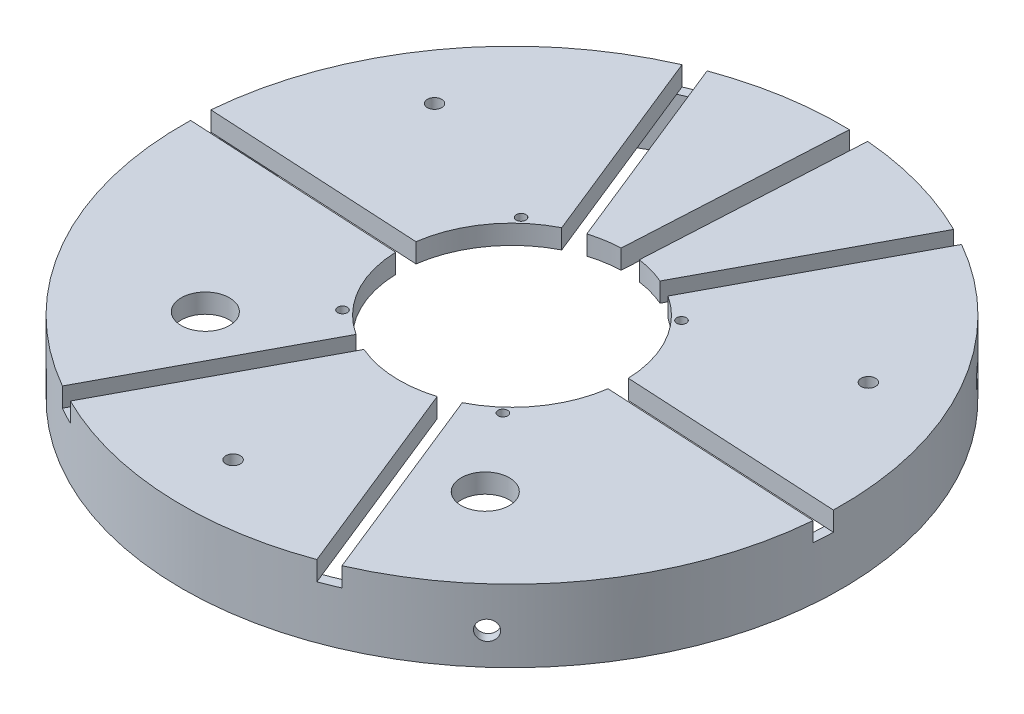
SolidWorks part; units mm, degrees
material "6061 Alloy"
ref_plane "Front Plane" through (0, 0, 0) normal (0, 0, 1) x (1, 0, 0)
ref_plane "Top Plane" through (0, 0, 0) normal (0, 1, 0) x (1, 0, 0)
ref_plane "Right Plane" through (0, 0, 0) normal (1, 0, 0) x (0, 0, -1)
sketch "Sketch1" plane through (0, 0, 0) normal (0, 1, 0) x (-0.9986, 0, -0.0535)
  line L0 (55.4987, 41.0091) -> (55.4987, 34.0091) construction
  line L2 (55.4987, -32.3449) -> (55.4987, -2.3278) construction
  circle A1 centre (55.4987, -32.3449) radius 68.37
  circle A3 centre (55.4987, -32.3449) radius 23.401
extrude "Boss-Extrude1" add sketch "Sketch1" along normal blind 2
sketch "Sketch3" plane through (0, 2, 0) normal (0, 1, 0) x (1, 0, 0)
  circle A0 centre (-53.6871, 35.2703) radius 68.37
  circle A1 centre (-53.6871, 35.2703) radius 66.37
extrude "Boss-Extrude2" add sketch "Sketch3" against normal blind 13
sketch "Sketch24" [suppressed] plane through (0, 4.3, 0) normal (0, 1, 0) x (1, 0, 0)
  line L0 (-34.4111, 2.0274) -> (-34.9466, -7.9582) construction
  line L1 (25.902, -11.2211) -> (26.4375, -1.2355) construction
  point P0 (-34.6788, -2.9654)
  point P1 (26.1698, -6.2283)
sketch "Sketch25" [suppressed] plane through (0, 0, 0) normal (0, -1, 0) x (1, 0, 0)
  point P0 (-34.6788, 2.9654)
  point P1 (26.1698, 6.2283)
ref_plane "Plane1" [suppressed] through (-0.258, 0, 4.8112) normal (0.0535, 0, -0.9986) x (-0.9986, 0, -0.0535)
sketch "Sketch29" [suppressed] plane through (0, 4.3, 0) normal (0, 1, 0) x (1, 0, 0)
  arc A0 (18.841, -0.8281) -> (-26.8146, 1.6201) centre (-4.2545, -4.5968) ccw construction
  arc A1 (-27.3501, -8.3656) -> (18.3055, -10.8138) centre (-4.2545, -4.5968) ccw construction
  point P0 (-3.0015, 18.7706)
  point P1 (-5.5076, -27.9643)
sketch "Sketch30" [suppressed] plane through (0, 0, 0) normal (0, -1, 0) x (1, 0, 0)
  point P0 (-5.5076, 27.9643)
  point P1 (-3.0015, -18.7706)
ref_plane "Plane2" [suppressed] through (-3.9965, 0, -0.2143) normal (-0.9986, 0, -0.0535) x (-0.0535, 0, 0.9986)
sketch "Sketch35" [suppressed] plane through (0, 0, 0) normal (0, 1, 0) x (1, 0, 0)
  line L0 (-3.8699, 2.5759) -> (-4.1232, -2.1473) construction
  line L1 (2.1036, -4.9378) -> (-2.6196, -4.6845) construction
  line L2 (20.5267, 17.662) -> (-4.2545, -4.5968) construction
  line L3 (-4.2545, -4.5968) -> (-31.1135, -28.7219) construction
  arc A1 (-27.3501, -8.3656) -> (18.3055, -10.8138) centre (-4.2545, -4.5968) ccw construction
  point P0 (-4.2545, -4.5968)
  point P8 (20.5267, 17.662)
  point P10 (-21.6638, -20.2341)
sketch "Sketch36" [suppressed] plane through (0, 4.3, 0) normal (0, 1, 0) x (1, 0, 0)
  point P0 (20.5267, 17.662)
ref_plane "Plane3" [suppressed] through (0.3855, 0, 0.4291) normal (0.6682, 0, 0.744) x (0.744, 0, -0.6682)
sketch "Sketch37" [suppressed] plane through (0, 4.3, 0) normal (0, 1, 0) x (1, 0, 0)
  line L1 (-26.6296, 20.3138) -> (-4.2545, -4.5968) construction
  line L2 (-4.2545, -4.5968) -> (20.7564, -32.4421) construction
  point P0 (-4.2545, -4.5968)
  point P7 (-26.6296, 20.3138)
sketch "Sketch39" [suppressed] plane through (0, 0, 0) normal (0, -1, 0) x (1, 0, 0)
  point P0 (-26.6296, -20.3138)
ref_plane "Plane4" [suppressed] through (-4.64, 0, 4.1677) normal (-0.744, 0, 0.6682) x (0.6682, 0, 0.744)
sketch "Sketch40" [suppressed] plane through (0.3855, 0, 0.4291) normal (0.6682, 0, 0.744) x (0.744, 0, -0.6682)
  circle A0 centre (-6.2369, -3.85) radius 2
extrude "Cut-Extrude27" [suppressed] cut sketch "Sketch40" against normal through all
pattern_circular "CirPattern2" [suppressed] count 4 over 360 reverse direction yes of bodies 107
sketch "Sketch58" plane through (0, 2, 0) normal (0, 1, 0) x (1, 0, 0)
  line L2 (-12.7238, 29.0656) -> (-12.2954, 37.0565)
  line L3 (-12.2954, 37.0565) -> (-7.3025, 36.7887)
  line L4 (-7.3025, 36.7887) -> (-7.731, 28.7979)
  line L5 (-7.731, 28.7979) -> (-12.7238, 29.0656)
sketch "Sketch60" plane through (0, 2, 0) normal (0, 1, 0) x (1, 0, 0)
  line L0 (-52.2437, 62.1872) -> (-55.1305, 8.3534) construction
  line L1 (-84.1539, 36.904) -> (-23.2203, 33.6365) construction
  line L4 (-73.7408, 17.2578) -> (-104.5394, -10.4059) construction
  line L5 (-53.6871, 35.2703) -> (-73.7408, 17.2578) construction
  line L6 (-71.6996, 55.324) -> (-99.3633, 86.1226) construction
  line L7 (-53.6871, 35.2703) -> (-71.6996, 55.324) construction
  line L8 (-33.6334, 53.2828) -> (-2.8348, 80.9464) construction
  line L9 (-53.6871, 35.2703) -> (-33.6334, 53.2828) construction
  line L10 (-35.6746, 15.2165) -> (-8.0109, -15.5821) construction
  line L11 (-53.6871, 35.2703) -> (-35.6746, 15.2165) construction
  line L12 (-73.7408, 17.2578) -> (-104.5394, -10.4059) construction
  line L13 (-53.6871, 35.2703) -> (-73.7408, 17.2578) construction
  arc A1 (-55.1305, 8.3534) -> (-80.604, 36.7136) centre (-53.6871, 35.2703) cw
  dimension "D1" = 4
sketch "Sketch62" plane through (0, 0, 0) normal (0, -1, 0) x (1, 0, 0)
  line L0 (-8.0109, 15.5821) -> (-99.3633, -86.1226) construction
  line L1 (-104.5394, 10.4059) -> (-2.8348, -80.9464) construction
  point P9 (-53.6871, -35.2703)
ref_plane "Plane5" through (-41.5069, 0, -46.2106) normal (0.6682, 0, 0.744) x (0.744, 0, -0.6682)
ref_plane "Plane6" through (-12.1802, 0, 10.9404) normal (0.744, 0, -0.6682) x (-0.6682, 0, -0.744)
sketch "Sketch63" plane through (-41.5069, 0, -46.2106) normal (0.6682, 0, 0.744) x (0.744, 0, -0.6682)
  line L0 (-84.7262, 0) -> (51.9818, 0) construction
  line L3 (-16.3722, 0) -> (-16.3722, -8.7) construction
  circle A0 centre (-16.3722, -4.35) radius 2
extrude "Cut-Extrude40" cut sketch "Sketch63" against normal through all and the other way through all
sketch "Sketch64" plane through (-12.1802, 0, 10.9404) normal (0.744, 0, -0.6682) x (-0.6682, 0, -0.744)
  line L0 (-6.2392, 0) -> (130.4688, 0) construction
  line L3 (62.1148, 0) -> (62.1148, -8.7) construction
  circle A0 centre (62.1148, -4.35) radius 2
extrude "Cut-Extrude41" cut sketch "Sketch64" against normal through all and the other way through all
sketch "Sketch65" plane through (0, 2, 0) normal (0, -1, 0) x (1, 0, 0)
  line L2 (1.1947, -31.5296) -> (-6.7555, -31.9265)
  line L3 (0.4048, -1118.9656) -> (-50.8954, -91.2006) construction
  line L4 (1.2944, -33.5271) -> (-6.7555, -33.9289)
  line L5 (-108.5689, -39.0109) -> (-100.6187, -38.6141)
  line L6 (-108.6686, -37.0134) -> (-100.6187, -36.6116)
  line L7 (-49.9465, -90.152) -> (-50.3433, -82.2019)
  line L8 (-51.944, -90.2517) -> (-52.3458, -82.2019)
  line L16 (-57.4277, 19.6115) -> (-57.0309, 11.6614) [skipped]
  line L17 (-55.4302, 19.7112) -> (-55.0284, 11.6614) [skipped]
  arc A2 (1.2944, -33.5271) -> (1.1947, -31.5296) centre (1.2445, -32.5284) ccw
  arc A3 (-6.7555, -33.9289) -> (-6.7555, -31.9265) centre (-6.8055, -32.9277) cw
  arc A4 (-51.944, -90.2517) -> (-49.9465, -90.152) centre (-50.9452, -90.2019) ccw
  arc A5 (-52.3458, -82.2019) -> (-50.3433, -82.2019) centre (-51.3445, -82.1519) cw
  arc A6 (-108.6686, -37.0134) -> (-108.5689, -39.0109) centre (-108.6187, -38.0121) ccw
  arc A7 (-100.6187, -36.6116) -> (-100.6187, -38.6141) centre (-100.5687, -37.6128) cw
  arc A16 (-55.4302, 19.7112) -> (-57.4277, 19.6115) centre (-56.429, 19.6614) ccw [skipped]
  arc A17 (-55.0284, 11.6614) -> (-57.0309, 11.6614) centre (-56.0297, 11.6114) cw [skipped]
  dimension "D1" = 4
sketch "Sketch67" plane through (0, 2, 0) normal (0, 1, 0) x (1, 0, 0)
  line L0 (-99.6611, 37.7404) -> (-7.7126, 32.8099) construction
  line L1 (-51.2218, 81.2445) -> (-56.1524, -10.704) construction
  line L2 (-47.8311, 125.7094) -> (-49.8283, 125.8165)
  line L3 (-144.1262, 41.1262) -> (-144.2333, 39.1291)
  line L4 (-99.6075, 38.739) -> (-144.1262, 41.1262)
  line L5 (-99.7146, 36.7419) -> (-144.2333, 39.1291)
  line L6 (-50.2184, 81.1907) -> (-47.8311, 125.7094)
  line L7 (-52.2155, 81.2978) -> (-49.8283, 125.8165)
  line L8 (36.752, 29.4143) -> (36.8591, 31.4114)
  line L9 (-7.7667, 31.8015) -> (36.752, 29.4143)
  line L10 (-7.6596, 33.7987) -> (36.8591, 31.4114)
  line L49 (-59.5431, -55.1689) -> (-57.5459, -55.276) [skipped]
  line L50 (-57.1558, -10.6501) -> (-59.5431, -55.1689) [skipped]
  line L51 (-55.1587, -10.7572) -> (-57.5459, -55.276) [skipped]
  arc A1 (-99.6075, 38.739) -> (-99.7146, 36.7419) centre (-99.6611, 37.7404) cw
  arc A2 (-50.2184, 81.1907) -> (-52.2155, 81.2978) centre (-51.2169, 81.2442) cw
  arc A3 (-7.7667, 31.8015) -> (-7.6596, 33.7987) centre (-7.7132, 32.8001) cw
  arc A8 (-57.1558, -10.6501) -> (-55.1587, -10.7572) centre (-56.1573, -10.7037) cw [skipped]
  dimension "D1" = 4
extrude "Cut-Extrude45" cut sketch "Sketch67" against normal blind 2
sketch "Sketch70" plane through (0, 2, 0) normal (0, 1, 0) x (1, 0, 0)
  line L0 (-51.2169, 81.2442) -> (-53.6871, 35.2703) construction
  line L1 (-99.6611, 37.7404) -> (-7.7132, 32.8001) construction
  line L2 (-53.6871, 35.2703) -> (-56.5307, -17.6534) construction
  circle A0 centre (-99.7745, 65.2862) radius 1.5
  circle A1 centre (-56.638, -19.6505) radius 1.5
  circle A2 centre (-4.6489, 60.1751) radius 1.5
  dimension "D1" = 3
  dimension "D2" = 3
sketch "Sketch72" plane through (0, 2, 0) normal (0, 1, 0) x (1, 0, 0)
  line L0 (-51.2169, 81.2442) -> (-56.638, -19.6505) construction
  line L1 (-99.6611, 37.7404) -> (-7.7132, 32.8001) construction
sketch "Sketch73" plane through (0, 2, 0) normal (0, -1, 0) x (1, 0, 0)
  circle A0 centre (-72.2141, -18.6326) radius 1
  circle A1 centre (-37.0495, -16.7433) radius 1
  circle A2 centre (-35.1601, -51.9079) radius 1
  circle A3 centre (-70.3247, -53.7973) radius 1
extrude "Cut-Extrude47" cut sketch "Sketch73" along normal blind 10
extrude "Cut-Extrude48" cut sketch "Sketch70" against normal blind 10
extrude "Cut-Extrude49" cut sketch "Sketch74" against normal blind 10
sketch "Sketch74" plane through (19.5625, 3, -2.0536) normal (0, 1, 0) x (1, 0, 0)
  line L0 (-73.2496, 33.2167) -> (-76.2005, -21.7041) construction
  line L1 (-73.2496, 33.2167) -> (-44.3242, -1.2553) construction
  line L2 (-73.2496, 33.2167) -> (-105.7022, 2.0425) construction
  circle A0 centre (-105.7022, 2.0425) radius 5
  circle A1 centre (-44.3242, -1.2553) radius 5
sketch "Sketch75" plane through (0, 2, 0) normal (0, 1, 0) x (1, 0, 0)
  line L0 (-50.0757, 102.5274) -> (-51.2185, 81.2443) construction
  line L1 (-120.9442, 38.8817) -> (13.57, 31.6588) construction
  line L2 (-86.2666, -23.6885) -> (-88.9936, -28.8014)
  line L3 (-22.8723, 95.1703) -> (-32.9078, 76.3546)
  line L4 (-21.1076, 94.229) -> (-31.1431, 75.4134)
  line L5 (-88.9936, -28.8014) -> (-87.2289, -29.7426)
  line L6 (-53.5602, 37.6331) -> (-58.8341, -60.585) construction
  line L7 (-52.5853, 35.2111) -> (-52.8048, 34.7997)
  line L8 (-84.5019, -24.6297) -> (-87.2289, -29.7426)
  line L9 (-79.7658, 97.3787) -> (-83.5737, 106.8386)
  line L10 (-53.5602, 37.6331) -> (-54.5694, 35.7409)
  line L11 (-77.9105, 98.1256) -> (-82.0529, 108.4166)
  line L12 (-79.7658, 97.3787) -> (-71.8029, 77.5967)
  line L13 (-22.8723, 95.1703) -> (-17.9091, 104.4757)
  line L14 (-77.9105, 98.1256) -> (-69.9475, 78.3435)
  line L15 (-27.6084, -26.8382) -> (-35.5714, -7.0562)
  line L16 (-21.1076, 94.229) -> (-18.0109, 100.0352)
  line L17 (-29.4638, -27.5851) -> (-37.4267, -7.803)
  line L18 (-29.4638, -27.5851) -> (-27.0828, -33.5)
  line L19 (-84.5019, -24.6297) -> (-74.4664, -5.8141)
  line L20 (-86.2666, -23.6885) -> (-76.2311, -4.8729)
  line L21 (-27.6084, -26.8382) -> (-25.2275, -32.7531)
  line L22 (-25.2275, -32.7531) -> (-27.0828, -33.5)
  line L23 (-83.5737, 106.8386) -> (-82.0529, 108.4166)
  line L24 (-17.9091, 104.4757) -> (-18.0109, 100.0352)
  arc A3 (-32.9078, 76.3546) -> (-31.1431, 75.4134) centre (-32.0254, 75.884) ccw
  arc A4 (-69.9475, 78.3435) -> (-71.8029, 77.5967) centre (-70.8752, 77.9701) cw
  arc A5 (-37.4267, -7.803) -> (-35.5714, -7.0562) centre (-36.499, -7.4296) cw
  arc A6 (-74.4664, -5.8141) -> (-76.2311, -4.8729) centre (-75.3488, -5.3435) ccw
extrude "Cut-Extrude51" cut sketch "Sketch75" against normal blind 2 contours A4 L14 L12 | L3 A3 L4 | L19 A6 L20 | A5 L17 L15 region at (-81.5448, 2, 16.9605) region at (-25.1869, 2, -88.7515) region at (-76.6935, 2, -92.4365) region at (-31.4741, 2, 19.913)
sketch "Sketch80" plane through (0, 2, 0) normal (0, 1, 0) x (1, 0, 0)
  line L0 (-121.8978, 39.9343) -> (-99.6075, 38.739)
  line L1 (-122.0051, 37.9371) -> (-99.7146, 36.7419)
  line L2 (-78.2871, 99.0613) -> (-69.9475, 78.3435)
  line L3 (-80.1424, 98.3145) -> (-71.8029, 77.5967)
  line L4 (-51.0202, 103.5882) -> (-52.2155, 81.2978)
  line L5 (-49.0231, 103.481) -> (-50.2184, 81.1907)
  line L6 (-22.3976, 96.0603) -> (-32.9078, 76.3546)
  line L7 (-20.6329, 95.119) -> (-31.1431, 75.4134)
  line L8 (-20.6329, 95.119) -> (-31.1431, 75.4134) construction
  line L9 (14.6309, 32.6034) -> (-7.6596, 33.7987)
  line L10 (-7.7667, 31.8015) -> (14.5236, 30.6063)
  line L11 (-86.7413, -24.5785) -> (-76.2311, -4.8729)
  line L12 (-74.4664, -5.8141) -> (-84.9766, -25.5197)
  line L13 (-37.4267, -7.803) -> (-29.0871, -28.5208)
  line L14 (-35.5714, -7.0562) -> (-27.2318, -27.7739)
  arc A0 (-80.1424, 98.3145) -> (-121.8978, 39.9343) centre (-53.6871, 35.2703) ccw
  circle A1 centre (-99.7745, 65.2862) radius 1.5
  circle A2 centre (-4.6489, 60.1751) radius 1.5
  circle A3 centre (-24.7617, 0.7983) radius 5
  circle A4 centre (-86.1397, 4.0961) radius 5
  circle A5 centre (-72.2141, 18.6326) radius 1
  circle A6 centre (-53.6871, 35.2703) radius 23.401
  circle A7 centre (-37.0495, 16.7433) radius 1
  circle A8 centre (-35.1601, 51.9079) radius 1
  circle A9 centre (-70.3247, 53.7973) radius 1
  arc A10 (-32.9078, 76.3546) -> (-31.1431, 75.4134) centre (-32.0254, 75.884) ccw construction
  circle A11 centre (-56.638, -19.6505) radius 1.5
  arc A12 (-7.7667, 31.8015) -> (-7.6596, 33.7987) centre (-7.7132, 32.8001) cw
  arc A13 (-32.9078, 76.3546) -> (-31.1431, 75.4134) centre (-32.0254, 75.884) ccw
  arc A14 (-52.2155, 81.2978) -> (-50.2184, 81.1907) centre (-51.2169, 81.2442) ccw
  arc A15 (-69.9475, 78.3435) -> (-71.8029, 77.5967) centre (-70.8752, 77.9701) cw
  arc A16 (-99.6075, 38.739) -> (-99.7146, 36.7419) centre (-99.6611, 37.7404) cw
  arc A17 (-74.4664, -5.8141) -> (-76.2311, -4.8729) centre (-75.3488, -5.3435) ccw
  arc A18 (-51.0202, 103.5882) -> (-78.2871, 99.0613) centre (-53.6871, 35.2703) ccw
  arc A19 (-76.2311, -4.8729) -> (-74.4664, -5.8141) centre (-75.3488, -5.3435) cw
  arc A20 (-35.5714, -7.0562) -> (-37.4267, -7.803) centre (-36.499, -7.4296) ccw
  arc A21 (-22.3976, 96.0603) -> (-49.0231, 103.481) centre (-53.6871, 35.2703) ccw
  arc A22 (14.6309, 32.6034) -> (-20.6329, 95.119) centre (-53.6871, 35.2703) ccw
  arc A23 (-27.2318, -27.7739) -> (14.5236, 30.6063) centre (-53.6871, 35.2703) ccw
  arc A24 (-84.9766, -25.5197) -> (-29.0871, -28.5208) centre (-53.6871, 35.2703) ccw
  arc A25 (-122.0051, 37.9371) -> (-86.7413, -24.5785) centre (-53.6871, 35.2703) ccw
  circle M1 centre (-24.7617, 0.7983) radius 5
  circle M2 centre (-86.1397, 4.0961) radius 5
  circle M3 centre (-4.6489, 60.1751) radius 1.5
  circle M4 centre (-99.7745, 65.2862) radius 1.5
  circle M5 centre (-56.638, -19.6505) radius 1.5
  circle M6 centre (-35.1601, 51.9079) radius 1
  circle M7 centre (-72.2141, 18.6326) radius 1
  circle M8 centre (-53.6871, 35.2703) radius 23.401
  circle M9 centre (-37.0495, 16.7433) radius 1
  circle M10 centre (-70.3247, 53.7973) radius 1
  arc M11 (-37.4267, -7.803) -> (-35.5714, -7.0562) centre (-36.499, -7.4296) cw
  line M12 (-35.5714, -7.0562) -> (-27.2318, -27.7739)
  arc M13 (-27.2318, -27.7739) -> (14.5236, 30.6063) centre (-53.6871, 35.2703) ccw
  line M14 (14.5236, 30.6063) -> (-7.7667, 31.8015)
  arc M15 (-7.7667, 31.8015) -> (-7.6596, 33.7987) centre (-7.7132, 32.8001) cw
  line M16 (-7.6596, 33.7987) -> (14.6309, 32.6034)
  arc M17 (14.6309, 32.6034) -> (-20.6329, 95.119) centre (-53.6871, 35.2703) ccw
  line M18 (-20.6329, 95.119) -> (-31.1431, 75.4134)
  arc M19 (-31.1431, 75.4134) -> (-32.9078, 76.3546) centre (-32.0254, 75.884) cw
  line M20 (-32.9078, 76.3546) -> (-22.3976, 96.0603)
  arc M21 (-22.3976, 96.0603) -> (-49.0231, 103.481) centre (-53.6871, 35.2703) ccw
  line M22 (-49.0231, 103.481) -> (-50.2184, 81.1907)
  arc M23 (-50.2184, 81.1907) -> (-52.2155, 81.2978) centre (-51.2169, 81.2442) cw
  line M24 (-52.2155, 81.2978) -> (-51.0202, 103.5882)
  arc M25 (-51.0202, 103.5882) -> (-78.2871, 99.0613) centre (-53.6871, 35.2703) ccw
  line M26 (-78.2871, 99.0613) -> (-69.9475, 78.3435)
  arc M27 (-69.9475, 78.3435) -> (-71.8029, 77.5967) centre (-70.8752, 77.9701) cw
  line M28 (-71.8029, 77.5967) -> (-80.1424, 98.3145)
  arc M29 (-80.1424, 98.3145) -> (-121.8978, 39.9343) centre (-53.6871, 35.2703) ccw
  line M30 (-121.8978, 39.9343) -> (-99.6075, 38.739)
  arc M31 (-99.6075, 38.739) -> (-99.7146, 36.7419) centre (-99.6611, 37.7404) cw
  line M32 (-99.7146, 36.7419) -> (-122.0051, 37.9371)
  arc M33 (-122.0051, 37.9371) -> (-86.7413, -24.5785) centre (-53.6871, 35.2703) ccw
  line M34 (-86.7413, -24.5785) -> (-76.2311, -4.8729)
  arc M35 (-76.2311, -4.8729) -> (-74.4664, -5.8141) centre (-75.3488, -5.3435) cw
  line M36 (-74.4664, -5.8141) -> (-84.9766, -25.5197)
  arc M37 (-84.9766, -25.5197) -> (-29.0871, -28.5208) centre (-53.6871, 35.2703) ccw
  line M38 (-29.0871, -28.5208) -> (-37.4267, -7.803)
extrude "Boss-Extrude4" add sketch "Sketch80" along normal blind 2 contours M38 M11 M12 M13 M14 M15 M16 M17 M18 M19 M20 M21 M22 M23 M24 M25 M26 M27 M28 M29 M30 M31 M32 M33 M34 M35 M36 M37 M2 M4 M6 M8 M10 M9 M7 M5 M3 M1 region at (-107.7243, 2, -73.9194)
sketch "Sketch81" plane through (0, 4, 0) normal (0, 1, 0) x (1, 0, 0)
  line L0 (-79.2175, 98.6947) -> (-28.1567, -28.1541) construction
  line L1 (-85.8624, -25.0556) -> (-21.5118, 95.5961) construction
  line L2 (14.5845, 31.6044) -> (-121.9588, 38.9361) construction
  line L3 (-50.0213, 103.5419) -> (-52.8071, 51.6586) construction
  line L4 (-79.2175, 98.6947) -> (-81.2506, 103.7454) construction
  line L5 (-50.0213, 103.5419) -> (-49.6564, 110.3364) construction
  line L6 (-21.5118, 95.5961) -> (-17.4008, 103.3039) construction
  line L7 (14.5845, 31.6044) -> (23.3386, 31.1344) construction
  line L8 (-28.1567, -28.1541) -> (-24.5898, -37.0153) construction
  line L9 (-85.8624, -25.0556) -> (-88.7119, -30.3981) construction
  line L10 (-121.9588, 38.9361) -> (-129.9907, 39.3674) construction
  line L11 (-81.0728, 97.9478) -> (-83.1059, 102.9986)
  line L12 (-81.0728, 97.9478) -> (-30.012, -28.901)
  line L13 (-30.012, -28.901) -> (-26.4451, -37.7621)
  line L14 (-52.0184, 103.6491) -> (-51.6536, 110.4437)
  line L15 (-52.0184, 103.6491) -> (-54.8043, 51.7658)
  line L16 (-84.0977, -25.9968) -> (-86.9472, -31.3394)
  line L17 (-84.0977, -25.9968) -> (-19.7471, 94.6549)
  line L18 (-19.7471, 94.6549) -> (-15.6361, 102.3627)
  line L19 (14.6918, 33.6015) -> (23.4459, 33.1315)
  line L20 (14.6918, 33.6015) -> (-121.8515, 40.9332)
  line L21 (-121.8515, 40.9332) -> (-129.8835, 41.3645)
  line L22 (-77.3622, 99.4415) -> (-79.3953, 104.4922)
  line L23 (-77.3622, 99.4415) -> (-26.3014, -27.4073)
  line L24 (-26.3014, -27.4073) -> (-22.7345, -36.2685)
  line L25 (-48.0241, 103.4347) -> (-47.6593, 110.2292)
  line L26 (-48.0241, 103.4347) -> (-50.81, 51.5514)
  line L27 (-87.6271, -24.1144) -> (-90.4766, -29.4569)
  line L28 (-87.6271, -24.1144) -> (-23.2765, 96.5373)
  line L29 (-23.2765, 96.5373) -> (-19.1655, 104.2451)
  line L30 (14.4773, 29.6073) -> (23.2314, 29.1373)
  line L31 (14.4773, 29.6073) -> (-122.066, 36.939)
  line L32 (-122.066, 36.939) -> (-130.098, 37.3702)
  line L33 (-83.1059, 102.9986) -> (-79.3953, 104.4922)
  line L34 (-51.6536, 110.4437) -> (-47.6593, 110.2292)
  line L35 (-19.1655, 104.2451) -> (-15.6361, 102.3627)
  line L36 (23.4459, 33.1315) -> (23.2314, 29.1373)
  line L37 (-26.4451, -37.7621) -> (-22.7345, -36.2685)
  line L38 (-90.4766, -29.4569) -> (-86.9472, -31.3394)
  line L39 (-129.8835, 41.3645) -> (-130.098, 37.3702)
  line L40 (-54.8043, 51.7658) -> (-50.81, 51.5514)
  arc A6 (-78.2871, 99.0613) -> (-80.1424, 98.3145) centre (-53.6871, 35.2703) ccw construction
  arc A7 (-29.0871, -28.5208) -> (-27.2318, -27.7739) centre (-53.6871, 35.2703) ccw construction
  arc A8 (-86.7413, -24.5785) -> (-84.9766, -25.5197) centre (-53.6871, 35.2703) ccw construction
  arc A9 (-20.6329, 95.119) -> (-22.3976, 96.0603) centre (-53.6871, 35.2703) ccw construction
  arc A11 (-121.8978, 39.9343) -> (-122.0051, 37.9371) centre (-53.6871, 35.2703) ccw construction
  arc A12 (14.5236, 30.6063) -> (14.6309, 32.6034) centre (-53.6871, 35.2703) ccw construction
  arc A13 (-49.0231, 103.481) -> (-51.0202, 103.5882) centre (-53.6871, 35.2703) ccw construction
  dimension "D1" = 2
  dimension "D2" = 2
extrude "Cut-Extrude52" cut sketch "Sketch81" against normal blind 4 contours L20 L21 L39 L32 L31 L30 L36 L19 | L28 L29 L35 L18 L17 L16 L38 L27 | L12 L13 L37 L24 L23 L22 L33 L11 | L26 L40 L15 L14 L34 L25
